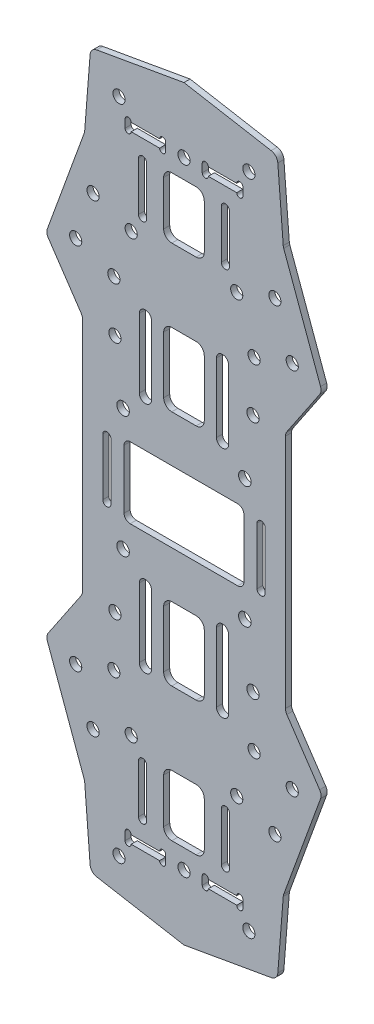
SolidWorks part; units mm, degrees
ref_plane "Front Plane" through (0, 0, 0) normal (0, 0, 1) x (1, 0, 0)
ref_plane "Top Plane" through (0, 0, 0) normal (0, 1, 0) x (1, 0, 0)
ref_plane "Right Plane" through (0, 0, 0) normal (1, 0, 0) x (0, 0, -1)
sketch "Sketch1" plane through (0, 0, 0) normal (0, 0, 1) x (1, 0, 0)
  line L0 (20, 7) -> (20, -7)
  line L1 (18, -7) -> (18, 7)
  line L2 (-18, 7) -> (-18, -7)
  line L3 (-20, -7) -> (-20, 7)
  line L4 (-11.2, -70.25) -> (-11.2, -58.25)
  line L5 (-9.2, -58.25) -> (-9.2, -70.25)
  line L6 (-11, -37.25) -> (-11, -20.25)
  line L7 (-8, -20.25) -> (-8, -37.25)
  line L8 (8, -37.25) -> (8, -20.25)
  line L9 (11, -20.25) -> (11, -37.25)
  line L10 (9.2, -70.25) -> (9.2, -58.25)
  line L11 (11.2, -58.25) -> (11.2, -70.25)
  line L12 (-3, -20.25) -> (3, -20.25)
  line L13 (5, -22.25) -> (5, -36.25)
  line L14 (3, -38.25) -> (-3, -38.25)
  line L15 (-5, -36.25) -> (-5, -22.25)
  line L16 (5, -58.25) -> (5, -69.25)
  line L17 (3, -71.25) -> (-3, -71.25)
  line L18 (-5, -69.25) -> (-5, -58.25)
  line L19 (-3, -56.25) -> (3, -56.25)
  line L20 (11.2, 70.25) -> (11.2, 58.25)
  line L21 (9.2, 58.25) -> (9.2, 70.25)
  line L22 (11, 37.25) -> (11, 20.25)
  line L23 (8, 20.25) -> (8, 37.25)
  line L24 (-8, 37.25) -> (-8, 20.25)
  line L25 (-11, 20.25) -> (-11, 37.25)
  line L26 (-9.2, 70.25) -> (-9.2, 58.25)
  line L27 (-11.2, 58.25) -> (-11.2, 70.25)
  line L28 (13.25, -8.75) -> (-13.25, -8.75)
  line L29 (-14.75, -7.25) -> (-14.75, 7.25)
  line L30 (-13.25, 8.75) -> (13.25, 8.75)
  line L31 (14.75, 7.25) -> (14.75, -7.25)
  line L32 (-5, 58.25) -> (-5, 69.25)
  line L33 (-3, 71.25) -> (3, 71.25)
  line L34 (5, 69.25) -> (5, 58.25)
  line L35 (3, 56.25) -> (-3, 56.25)
  line L36 (-3, 38.25) -> (3, 38.25)
  line L37 (5, 36.25) -> (5, 22.25)
  line L38 (3, 20.25) -> (-3, 20.25)
  line L39 (-5, 22.25) -> (-5, 36.25)
  line L40 (-24.5714, 68.9048) -> (-33.6515, 43.9576)
  line L41 (-33.4302, 42.1552) -> (-25.3419, 30.1639)
  line L42 (-25, 29.0455) -> (-25, -29.0455)
  line L43 (-25.3419, -30.1639) -> (-33.4302, -42.1552)
  line L44 (-33.6515, -43.9576) -> (-24.5714, -68.9048)
  line L45 (-24.457, -69.4319) -> (-23.1215, -86.4007)
  line L46 (-21.475, -88.2134) -> (0, -92)
  line L47 (0, -92) -> (21.475, -88.2134)
  line L48 (23.1215, -86.4007) -> (24.457, -69.4319)
  line L49 (24.5714, -68.9048) -> (33.6515, -43.9576)
  line L50 (33.4302, -42.1552) -> (25.3419, -30.1639)
  line L51 (25, -29.0455) -> (25, 29.0455)
  line L52 (25.3419, 30.1639) -> (33.4302, 42.1552)
  line L53 (33.6515, 43.9576) -> (24.5714, 68.9048)
  line L54 (24.457, 69.4319) -> (23.1215, 86.4007)
  line L55 (21.475, 88.2134) -> (0, 92)
  line L56 (0, 92) -> (-21.475, 88.2134)
  line L57 (-23.1215, 86.4007) -> (-24.457, 69.4319)
  line L58 (-14.5, 75) -> (-14.5, 77)
  line L59 (-13, 77) -> (-6, 77)
  line L60 (-4.5, 77) -> (-4.5, 75)
  line L61 (-6, 75) -> (-13, 75)
  line L62 (6, 77) -> (13, 77)
  line L63 (14.5, 77) -> (14.5, 75)
  line L64 (13, 75) -> (6, 75)
  line L65 (4.5, 75) -> (4.5, 77)
  line L66 (13, -77) -> (6, -77)
  line L67 (4.5, -77) -> (4.5, -75)
  line L68 (6, -75) -> (13, -75)
  line L69 (14.5, -75) -> (14.5, -77)
  line L70 (-6, -77) -> (-13, -77)
  line L71 (-14.5, -77) -> (-14.5, -75)
  line L72 (-13, -75) -> (-6, -75)
  line L73 (-4.5, -75) -> (-4.5, -77)
  arc A0 (20, -7) -> (18, -7) centre (19, -7) cw
  arc A1 (18, 7) -> (20, 7) centre (19, 7) cw
  arc A2 (-18, -7) -> (-20, -7) centre (-19, -7) cw
  arc A3 (-20, 7) -> (-18, 7) centre (-19, 7) cw
  arc A4 (-11.2, -58.25) -> (-9.2, -58.25) centre (-10.2, -58.25) cw
  arc A5 (-9.2, -70.25) -> (-11.2, -70.25) centre (-10.2, -70.25) cw
  arc A6 (-11, -20.25) -> (-8, -20.25) centre (-9.5, -20.25) cw
  arc A7 (-8, -37.25) -> (-11, -37.25) centre (-9.5, -37.25) cw
  arc A8 (8, -20.25) -> (11, -20.25) centre (9.5, -20.25) cw
  arc A9 (11, -37.25) -> (8, -37.25) centre (9.5, -37.25) cw
  arc A10 (9.2, -58.25) -> (11.2, -58.25) centre (10.2, -58.25) cw
  arc A11 (11.2, -70.25) -> (9.2, -70.25) centre (10.2, -70.25) cw
  arc A12 (3, -20.25) -> (5, -22.25) centre (3, -22.25) cw
  arc A13 (5, -36.25) -> (3, -38.25) centre (3, -36.25) cw
  arc A14 (-3, -38.25) -> (-5, -36.25) centre (-3, -36.25) cw
  arc A15 (-5, -22.25) -> (-3, -20.25) centre (-3, -22.25) cw
  arc A16 (5, -69.25) -> (3, -71.25) centre (3, -69.25) cw
  arc A17 (-3, -71.25) -> (-5, -69.25) centre (-3, -69.25) cw
  arc A18 (-5, -58.25) -> (-3, -56.25) centre (-3, -58.25) cw
  arc A19 (3, -56.25) -> (5, -58.25) centre (3, -58.25) cw
  arc A20 (11.2, 58.25) -> (9.2, 58.25) centre (10.2, 58.25) cw
  arc A21 (9.2, 70.25) -> (11.2, 70.25) centre (10.2, 70.25) cw
  arc A22 (11, 20.25) -> (8, 20.25) centre (9.5, 20.25) cw
  arc A23 (8, 37.25) -> (11, 37.25) centre (9.5, 37.25) cw
  arc A24 (-8, 20.25) -> (-11, 20.25) centre (-9.5, 20.25) cw
  arc A25 (-11, 37.25) -> (-8, 37.25) centre (-9.5, 37.25) cw
  arc A26 (-9.2, 58.25) -> (-11.2, 58.25) centre (-10.2, 58.25) cw
  arc A27 (-11.2, 70.25) -> (-9.2, 70.25) centre (-10.2, 70.25) cw
  arc A28 (-13.25, -8.75) -> (-14.75, -7.25) centre (-13.25, -7.25) cw
  arc A29 (-14.75, 7.25) -> (-13.25, 8.75) centre (-13.25, 7.25) cw
  arc A30 (13.25, 8.75) -> (14.75, 7.25) centre (13.25, 7.25) cw
  arc A31 (14.75, -7.25) -> (13.25, -8.75) centre (13.25, -7.25) cw
  arc A32 (-5, 69.25) -> (-3, 71.25) centre (-3, 69.25) cw
  arc A33 (3, 71.25) -> (5, 69.25) centre (3, 69.25) cw
  arc A34 (5, 58.25) -> (3, 56.25) centre (3, 58.25) cw
  arc A35 (-3, 56.25) -> (-5, 58.25) centre (-3, 58.25) cw
  arc A36 (3, 38.25) -> (5, 36.25) centre (3, 36.25) cw
  arc A37 (5, 22.25) -> (3, 20.25) centre (3, 22.25) cw
  arc A38 (-3, 20.25) -> (-5, 22.25) centre (-3, 22.25) cw
  arc A39 (-5, 36.25) -> (-3, 38.25) centre (-3, 36.25) cw
  arc A40 (-24.457, 69.4319) -> (-24.5714, 68.9048) centre (-26.4508, 69.5889) cw
  arc A41 (-33.6515, 43.9576) -> (-33.4302, 42.1552) centre (-31.7721, 43.2736) ccw
  arc A42 (-25.3419, 30.1639) -> (-25, 29.0455) centre (-27, 29.0455) cw
  arc A43 (-25, -29.0455) -> (-25.3419, -30.1639) centre (-27, -29.0455) cw
  arc A44 (-33.4302, -42.1552) -> (-33.6515, -43.9576) centre (-31.7721, -43.2736) ccw
  arc A45 (-24.5714, -68.9048) -> (-24.457, -69.4319) centre (-26.4508, -69.5889) cw
  arc A46 (-23.1215, -86.4007) -> (-21.475, -88.2134) centre (-21.1277, -86.2438) ccw
  arc A47 (21.475, -88.2134) -> (23.1215, -86.4007) centre (21.1277, -86.2438) ccw
  arc A48 (24.457, -69.4319) -> (24.5714, -68.9048) centre (26.4508, -69.5889) cw
  arc A49 (33.6515, -43.9576) -> (33.4302, -42.1552) centre (31.7721, -43.2736) ccw
  arc A50 (25.3419, -30.1639) -> (25, -29.0455) centre (27, -29.0455) cw
  arc A51 (25, 29.0455) -> (25.3419, 30.1639) centre (27, 29.0455) cw
  arc A52 (33.4302, 42.1552) -> (33.6515, 43.9576) centre (31.7721, 43.2736) ccw
  arc A53 (24.5714, 68.9048) -> (24.457, 69.4319) centre (26.4508, 69.5889) cw
  arc A54 (23.1215, 86.4007) -> (21.475, 88.2134) centre (21.1277, 86.2438) ccw
  arc A55 (-21.475, 88.2134) -> (-23.1215, 86.4007) centre (-21.1277, 86.2438) ccw
  circle A56 centre (-16, 81) radius 1.5
  circle A57 centre (0, 76) radius 1.5
  circle A58 centre (-26.6722, 45.4202) radius 1.5
  circle A59 centre (-22.3969, 57.1664) radius 1.5
  circle A60 centre (-17.2753, 42) radius 1.5
  circle A61 centre (-13, 53.7462) radius 1.5
  circle A62 centre (-17, 29.5) radius 1.5
  circle A63 centre (-15.25, 15.25) radius 1.5
  circle A64 centre (15.25, 15.25) radius 1.5
  circle A65 centre (17, 29.5) radius 1.5
  circle A66 centre (13, 53.7462) radius 1.5
  circle A67 centre (17.2753, 42) radius 1.5
  circle A68 centre (22.3969, 57.1664) radius 1.5
  circle A69 centre (26.6722, 45.4202) radius 1.5
  circle A70 centre (16, 81) radius 1.5
  circle A71 centre (16, -81) radius 1.5
  circle A72 centre (26.6722, -45.4202) radius 1.5
  circle A73 centre (22.3969, -57.1664) radius 1.5
  circle A74 centre (17.2753, -42) radius 1.5
  circle A75 centre (13, -53.7462) radius 1.5
  circle A76 centre (17, -29.5) radius 1.5
  circle A77 centre (15.25, -15.25) radius 1.5
  circle A78 centre (-15.25, -15.25) radius 1.5
  circle A79 centre (-17, -29.5) radius 1.5
  circle A80 centre (-13, -53.7462) radius 1.5
  circle A81 centre (-17.2753, -42) radius 1.5
  circle A82 centre (-22.3969, -57.1664) radius 1.5
  circle A83 centre (-26.6722, -45.4202) radius 1.5
  circle A84 centre (0, -76) radius 1.5
  circle A85 centre (-16, -81) radius 1.5
  arc A86 (-13, 75) -> (-14.5, 75) centre (-13.75, 75) cw
  arc A87 (-14.5, 77) -> (-13, 77) centre (-13.75, 77) cw
  arc A88 (-6, 77) -> (-4.5, 77) centre (-5.25, 77) cw
  arc A89 (-4.5, 75) -> (-6, 75) centre (-5.25, 75) cw
  arc A90 (4.5, 77) -> (6, 77) centre (5.25, 77) cw
  arc A91 (13, 77) -> (14.5, 77) centre (13.75, 77) cw
  arc A92 (14.5, 75) -> (13, 75) centre (13.75, 75) cw
  arc A93 (6, 75) -> (4.5, 75) centre (5.25, 75) cw
  arc A94 (14.5, -77) -> (13, -77) centre (13.75, -77) cw
  arc A95 (6, -77) -> (4.5, -77) centre (5.25, -77) cw
  arc A96 (4.5, -75) -> (6, -75) centre (5.25, -75) cw
  arc A97 (13, -75) -> (14.5, -75) centre (13.75, -75) cw
  arc A98 (-4.5, -77) -> (-6, -77) centre (-5.25, -77) cw
  arc A99 (-13, -77) -> (-14.5, -77) centre (-13.75, -77) cw
  arc A100 (-14.5, -75) -> (-13, -75) centre (-13.75, -75) cw
  arc A101 (-6, -75) -> (-4.5, -75) centre (-5.25, -75) cw
extrude "bottom-plate" add sketch "Sketch1" against normal blind 1.5
sketch "Sketch2" plane through (0, 0, 0) normal (0, 0, 1) x (1, 0, 0)
  circle A0 centre (-15.25, 15.25) radius 1.5 construction
  circle A1 centre (15.25, 15.25) radius 1.5 construction
  circle A2 centre (-15.25, -15.25) radius 1.5 construction
  circle A3 centre (15.25, -15.25) radius 1.5 construction
  circle A4 centre (-15.25, 15.25) radius 1.5
  circle A5 centre (15.25, 15.25) radius 1.5
  circle A6 centre (-15.25, -15.25) radius 1.5
  circle A7 centre (15.25, -15.25) radius 1.5
extrude "Boss-Extrude2" add sketch "Sketch2" against normal up to surface (1.5 mm away) up to face at (-9.5, -76, -1.5)
sketch "Sketch4" plane through (0, 0, 0) normal (0, 0, 1) x (1, 0, 0)
  line L0 (0, 92) -> (0, -92) construction
  line L1 (-25, 0) -> (25, 0) construction
  line L2 (-25, 29.0455) -> (-25, -29.0455) construction
  line L3 (25, -29.0455) -> (25, 29.0455) construction
  circle A0 centre (-15, 15) radius 1.55
  circle A1 centre (15, 15) radius 1.55
  circle A2 centre (15, -15) radius 1.55
  circle A3 centre (-15, -15) radius 1.55
  dimension "D1" = 3.1
  dimension "D2" = 30
  dimension "D3" = 30
extrude "Cut-Extrude1" cut sketch "Sketch4" against normal up to next
